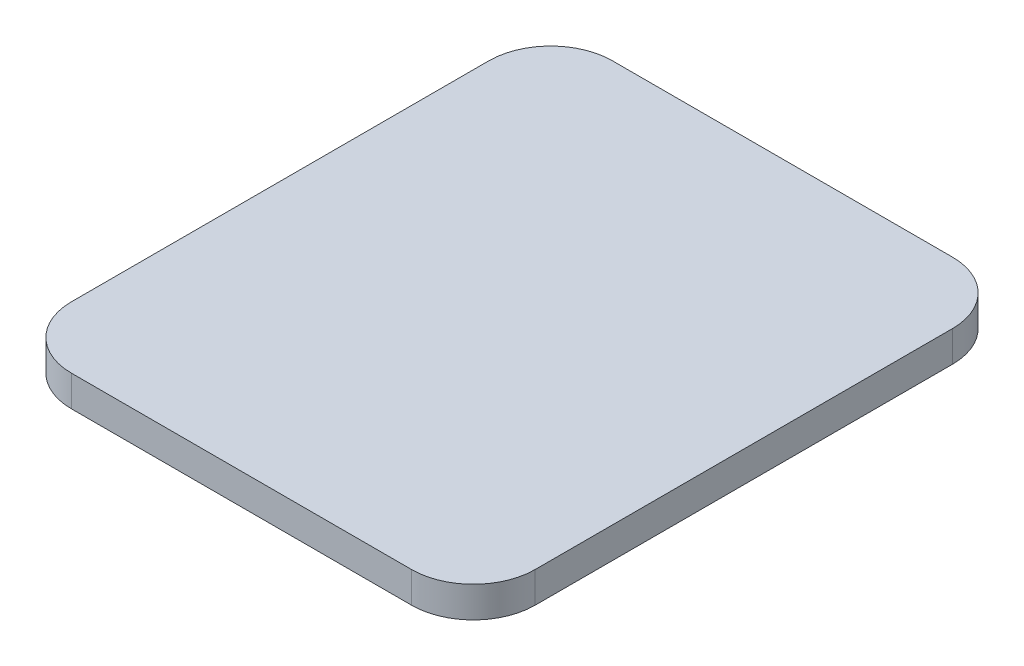
SolidWorks part; units mm, degrees
material "Кремний"
ref_plane "Спереди" through (0, 0, 0) normal (0, 0, 1) x (1, 0, 0)
ref_plane "Сверху" through (0, 0, 0) normal (0, 1, 0) x (1, 0, 0)
ref_plane "Справа" through (0, 0, 0) normal (1, 0, 0) x (0, 0, -1)
sketch "Эскиз экрана" plane through (0, 0, 0) normal (0, 1, 0) x (1, 0, 0)
  line L1 (-11, 17.5) -> (11, 17.5)
  line L2 (-15, 13.5) -> (-15, -13.5)
  line L3 (-11, -17.5) -> (11, -17.5)
  line L4 (15, 13.5) -> (15, -13.5)
  arc A0 (-15, -13.5) -> (-11, -17.5) centre (-11, -13.5) ccw
  arc A1 (11, -17.5) -> (15, -13.5) centre (11, -13.5) ccw
  arc A2 (11, 17.5) -> (15, 13.5) centre (11, 13.5) cw
  arc A3 (-11, 17.5) -> (-15, 13.5) centre (-11, 13.5) ccw
  point P7 (-15, -17.5)
  point P12 (15, 17.5)
  point P15 (-15, 17.5)
  dimension "D5" = 4
  dimension "D1" = 35
  dimension "D2" = 30
  dimension "D3" = 15
  dimension "D4" = 17.5
extrude "Экран" add sketch "Эскиз экрана" against normal blind 2
